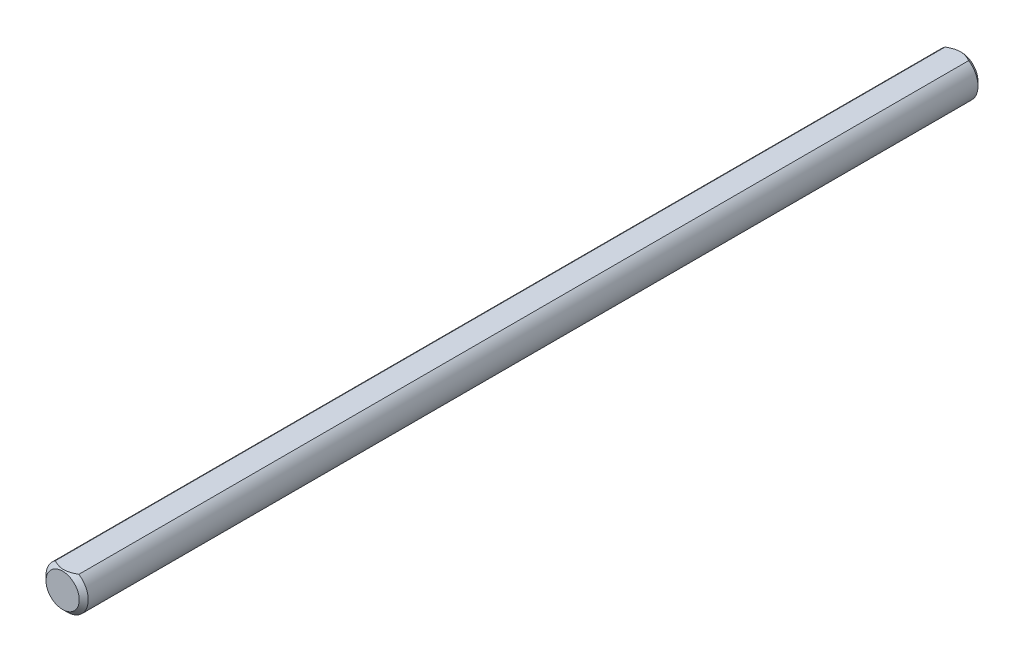
SolidWorks part; units mm, degrees
ref_plane "Front Plane" through (0, 0, 0) normal (0, 0, 1) x (1, 0, 0)
ref_plane "Top Plane" through (0, 0, 0) normal (0, 1, 0) x (1, 0, 0)
ref_plane "Right Plane" through (0, 0, 0) normal (1, 0, 0) x (0, 0, -1)
sketch "Sketch1" plane through (0, 0, 0) normal (0, 0, 1) x (1, 0, 0)
  line L0 (-1.3115, 1.95) -> (1.3115, 1.95)
  line L1 (-2.35, -2.35) -> (3.8521, -2.35) construction
  arc A0 (-1.3115, 1.95) -> (1.3115, 1.95) centre (0, 0) ccw
  dimension "D1" = 4.3
extrude "Boss-Extrude1" add sketch "Sketch1" along normal blind 100
chamfer "Chamfer1" distance 0.5 angle 45 2 edges at (0, -2.35, 0) (0, -2.35, 100)
